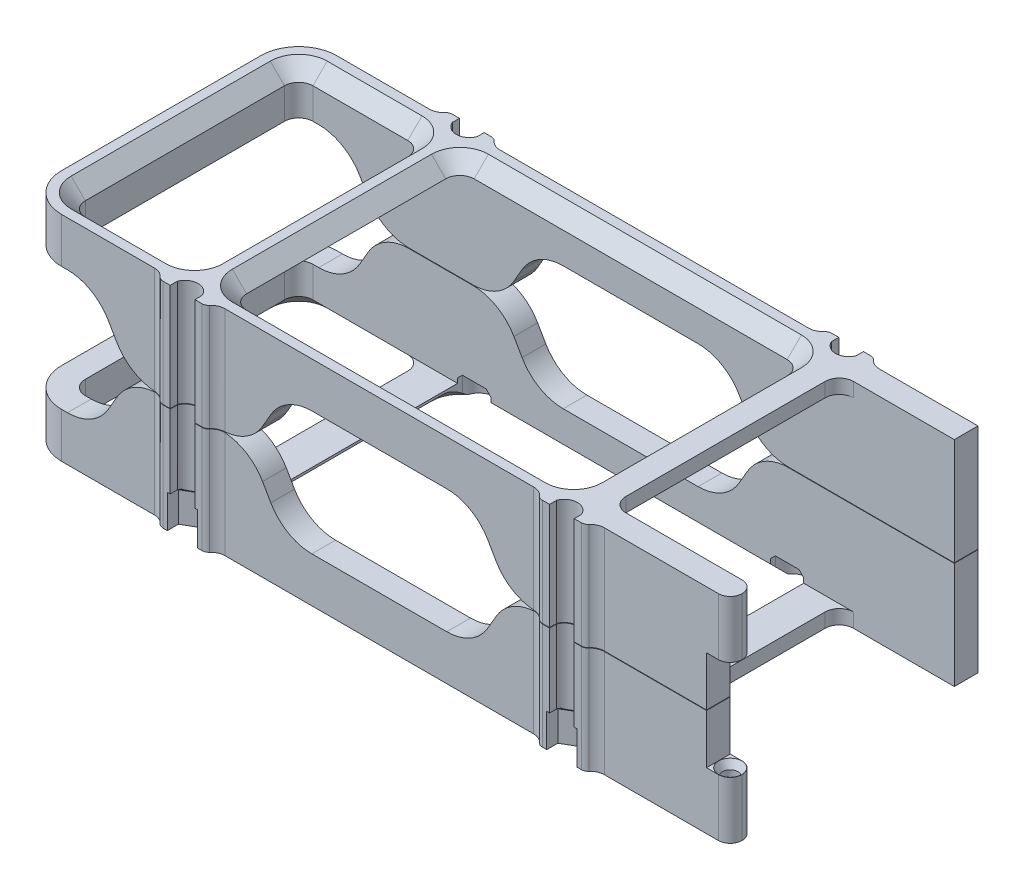
SolidWorks part; units mm, degrees
ref_plane "Płaszczyzna przednia" through (0, 0, 0) normal (0, 0, 1) x (1, 0, 0)
ref_plane "Płaszczyzna górna" through (0, 0, 0) normal (0, 1, 0) x (1, 0, 0)
ref_plane "Płaszczyzna prawa" through (0, 0, 0) normal (1, 0, 0) x (0, 0, -1)
sketch "Szkic1" plane through (0, 0, 0) normal (0, 1, 0) x (1, 0, 0)
  line L0 (-70, -24) -> (74, -24)
  line L1 (74, -24) -> (74, -29)
  line L3 (-75, -29) -> (-75, -24)
  line L4 (74, -29) -> (45.6, -29)
  line L5 (0, 29) -> (0, -29) construction
  line L6 (-34.4, -29) -> (34.4, -29)
  line L7 (-75, -29) -> (-45.6, -29)
  line L8 (-45.6, -29) -> (-40, -29) construction
  line L9 (-40, -29) -> (-34.4, -29) construction
  line L10 (34.4, -29) -> (40, -29) construction
  line L11 (45.6, -29) -> (40, -29) construction
  line L12 (-55, 0) -> (55, 0) construction
  line L13 (45.6, 29) -> (40, 29) construction
  line L14 (34.4, 29) -> (40, 29) construction
  line L15 (-40, 29) -> (-34.4, 29) construction
  line L16 (-45.6, 29) -> (-40, 29) construction
  line L17 (-75, 29) -> (-45.6, 29)
  line L18 (-34.4, 29) -> (34.4, 29)
  line L19 (68.25, 29) -> (45.6, 29)
  line L20 (-75, 29) -> (-75, 24)
  line L21 (74, 24) -> (74, 29) construction
  line L22 (-70, 24) -> (68.25, 24)
  line L23 (-75, 24) -> (-75, -24)
  line L24 (-70, 24) -> (-70, -24)
  line L25 (-75, 24) -> (-70, 24) construction
  line L26 (-75, -24) -> (-70, -24) construction
  line L27 (68.25, 29) -> (68.25, 24)
  line L28 (68.25, 24) -> (74, 24) construction
  line L29 (74, 29) -> (68.25, 29) construction
  arc A0 (-45.6, -29) -> (-34.4, -29) centre (-40, -29) ccw
  arc A1 (34.4, -29) -> (45.6, -29) centre (40, -29) ccw
  arc A2 (-34.4, -29) -> (-45.6, -29) centre (-40, -29) ccw construction
  arc A3 (45.6, -29) -> (34.4, -29) centre (40, -29) ccw construction
  arc A4 (45.6, 29) -> (34.4, 29) centre (40, 29) cw construction
  arc A5 (-34.4, 29) -> (-45.6, 29) centre (-40, 29) cw construction
  arc A6 (34.4, 29) -> (45.6, 29) centre (40, 29) cw
  arc A7 (-45.6, 29) -> (-34.4, 29) centre (-40, 29) cw
  point P4 (0, 0)
  point P12 (0, 0)
  point P16 (0, -29)
  point P31 (0, 29)
  dimension "D1" = 11.2
  dimension "D2" = 11.2
  dimension "D3" = 80
  dimension "D4" = 149
  dimension "D6" = 58
  dimension "D7" = 5
  dimension "D5" = 48
  dimension "D8" = 5.75
extrude "Dodanie-wyciągnięcie1" add sketch "Szkic1" along normal blind 22.5 separate body
sketch "Szkic2" plane through (0, 22.5, 0) normal (0, 1, 0) x (1, 0, 0)
  line L0 (-45.6, -29) -> (-42.6, -29) construction
  line L3 (-37.4, -29) -> (-34.4, -29) construction
  line L4 (-44.1, -30.5) -> (-42.6, -30.5)
  line L5 (-42.6, -29) -> (-42.6, -30.5)
  line L6 (-37.4, -29) -> (-37.4, -30.5)
  line L7 (-42.6, -30.5) -> (-42.1237, -30.5) construction
  line L8 (-42.1237, -30.5) -> (-37.8763, -30.5) construction
  line L9 (-37.8763, -30.5) -> (-37.4, -30.5) construction
  line L10 (-37.4, -30.5) -> (-35.9, -30.5)
  line L12 (-55, 0) -> (55, 0) construction
  line L13 (-37.8763, 30.5) -> (-37.4, 30.5) construction
  line L14 (-42.1237, 30.5) -> (-37.8763, 30.5) construction
  line L15 (-42.6, 30.5) -> (-42.1237, 30.5) construction
  line L16 (-37.4, 29) -> (-34.4, 29) construction
  line L22 (-45.6, 29) -> (-42.6, 29) construction
  line L23 (-37.4, 30.5) -> (-35.9, 30.5)
  line L24 (-37.4, 29) -> (-37.4, 30.5)
  line L25 (-42.6, 29) -> (-42.6, 30.5)
  line L26 (-44.1, 30.5) -> (-42.6, 30.5)
  line L27 (0, -55) -> (0, 55) construction
  line L28 (45.6, 29) -> (42.6, 29) construction
  line L29 (37.4, 29) -> (34.4, 29) construction
  line L30 (42.6, 30.5) -> (42.1237, 30.5) construction
  line L31 (42.1237, 30.5) -> (37.8763, 30.5) construction
  line L40 (37.8763, 30.5) -> (37.4, 30.5) construction
  line L41 (37.8763, -30.5) -> (37.4, -30.5) construction
  line L42 (42.1237, -30.5) -> (37.8763, -30.5) construction
  line L43 (42.6, -30.5) -> (42.1237, -30.5) construction
  line L44 (37.4, -29) -> (34.4, -29) construction
  line L45 (45.6, -29) -> (42.6, -29) construction
  line L46 (44.1, 30.5) -> (42.6, 30.5)
  line L47 (42.6, 29) -> (42.6, 30.5)
  line L48 (37.4, 29) -> (37.4, 30.5)
  line L49 (37.4, 30.5) -> (35.9, 30.5)
  line L50 (37.4, -30.5) -> (35.9, -30.5)
  line L51 (37.4, -29) -> (37.4, -30.5)
  line L52 (42.6, -29) -> (42.6, -30.5)
  line L53 (44.1, -30.5) -> (42.6, -30.5)
  arc A3 (-42.1237, -30.5) -> (-37.8763, -30.5) centre (-40, -29) ccw construction
  arc A4 (-45.6, -29) -> (-44.1, -30.5) centre (-44.1, -29) ccw
  arc A5 (-34.4, -29) -> (-35.9, -30.5) centre (-35.9, -29) cw
  arc A6 (-45.6, -29) -> (-34.4, -29) centre (-40, -29) ccw
  arc A7 (-42.6, -29) -> (-42.1237, -30.5) centre (-40, -29) ccw construction
  arc A8 (-37.8763, -30.5) -> (-37.4, -29) centre (-40, -29) ccw construction
  arc A10 (-37.8763, 30.5) -> (-37.4, 29) centre (-40, 29) cw construction
  arc A11 (-42.6, 29) -> (-42.1237, 30.5) centre (-40, 29) cw construction
  arc A12 (-42.1237, 30.5) -> (-37.8763, 30.5) centre (-40, 29) cw construction
  arc A17 (-42.6, 29) -> (-37.4, 29) centre (-40, 30) ccw
  arc A18 (-45.6, 29) -> (-34.4, 29) centre (-40, 29) cw
  arc A19 (-34.4, 29) -> (-35.9, 30.5) centre (-35.9, 29) ccw
  arc A20 (-45.6, 29) -> (-44.1, 30.5) centre (-44.1, 29) cw
  arc A21 (42.1237, 30.5) -> (37.8763, 30.5) centre (40, 29) ccw construction
  arc A22 (42.6, 29) -> (42.1237, 30.5) centre (40, 29) ccw construction
  arc A31 (-42.6, -29) -> (-37.4, -29) centre (-40, -30) cw
  arc A32 (37.8763, 30.5) -> (37.4, 29) centre (40, 29) ccw construction
  arc A33 (37.8763, -30.5) -> (37.4, -29) centre (40, -29) cw construction
  arc A34 (42.6, -29) -> (42.1237, -30.5) centre (40, -29) cw construction
  arc A35 (42.1237, -30.5) -> (37.8763, -30.5) centre (40, -29) cw construction
  arc A36 (42.6, -29) -> (37.4, -29) centre (40, -30) ccw
  arc A37 (45.6, 29) -> (44.1, 30.5) centre (44.1, 29) ccw
  arc A38 (34.4, 29) -> (35.9, 30.5) centre (35.9, 29) cw
  arc A39 (45.6, 29) -> (34.4, 29) centre (40, 29) ccw
  arc A40 (42.6, 29) -> (37.4, 29) centre (40, 30) cw
  arc A41 (45.6, -29) -> (34.4, -29) centre (40, -29) cw
  arc A42 (34.4, -29) -> (35.9, -30.5) centre (35.9, -29) ccw
  arc A43 (45.6, -29) -> (44.1, -30.5) centre (44.1, -29) cw
  dimension "D1" = 5.2
  dimension "D2" = 1
extrude "Wytnij-wyciągnięcie1" cut sketch "Szkic2" against normal through all
fillet "Zaokrąglenie1" radius 8 2 edges at (-75, 11.25, -29) (-75, 11.25, 29)
fillet "Zaokrąglenie2" radius 3 2 edges at (-70, 11.25, -24) (-70, 11.25, 24)
fillet "Zaokrąglenie3" radius 3 8 edges at (-34.4, 11.25, 29) (-45.6, 11.25, 29) (-45.6, 11.25, -29) (-34.4, 11.25, -29) (34.4, 11.25, -29) (45.6, 11.25, -29) (45.6, 11.25, 29) (34.4, 11.25, 29)
fillet "Zaokrąglenie4" radius 2.5 2 edges at (74, 11.25, 24) (74, 11.25, 29)
sketch "Szkic16" plane through (0, 0, 0) normal (0, -1, 0) x (1, 0, 0)
  line L0 (-40, 0) -> (40, 0) construction
  line L1 (40, 24) -> (40, -24) construction
  line L2 (-67, -24) -> (68.25, -24) construction
  line L4 (71.5, 24) -> (-67, 24) construction
  line L5 (44, 24) -> (44, -24)
  line L6 (44, -24) -> (40, -24)
  line L7 (36, 24) -> (44, 24)
  line L8 (36, 24) -> (36, -24)
  line L9 (36, -24) -> (40, -24)
  line L10 (0, -55) -> (0, 55) construction
  line L11 (-44, -24) -> (-40, -24)
  line L12 (-36, -24) -> (-40, -24)
  line L13 (-44, 24) -> (-44, -24)
  line L14 (-36, 24) -> (-44, 24)
  line L15 (-36, 24) -> (-36, -24)
  point P4 (0, 0)
  point P10 (40, 0)
  point P17 (40, 24)
  dimension "D1" = 80
  dimension "D2" = 8
extrude "Dodanie-wyciągnięcie6" add sketch "Szkic16" against normal blind 3
sketch "Szkic17" plane through (0, 0, 29) normal (0, 0, 1) x (1, 0, 0)
  line L0 (-75, 9.5) -> (-60, 9.5)
  line L1 (-75, 0) -> (-75, 22.5) construction
  line L2 (-60, 9.5) -> (-52.4944, 22.5)
  line L3 (-67, 22.5) -> (-47.4541, 22.5) construction
  line L4 (-52.4944, 22.5) -> (-75, 22.5)
  line L5 (-75, 22.5) -> (-75, 9.5)
  dimension "D1" = 15
  dimension "D2" = 60
  dimension "D3" = 13
extrude "Wytnij-wyciągnięcie9" cut sketch "Szkic17" against normal through all
sketch "Szkic18" plane through (0, 0, 29) normal (0, 0, 1) x (1, 0, 0)
  line L0 (-27.5056, 22.5) -> (-20, 9.5)
  line L1 (-32.5459, 22.5) -> (32.5459, 22.5) construction
  line L2 (0, 0) -> (0, 9.5) construction
  line L3 (-32.5459, 0) -> (32.5459, 0) construction
  line L4 (20, 9.5) -> (-20, 9.5)
  line L5 (20, 9.5) -> (27.5056, 22.5)
  line L6 (27.5056, 22.5) -> (-27.5056, 22.5)
  point P11 (0, 9.5)
  dimension "D1" = 60
  dimension "D2" = 60
  dimension "D3" = 40
  dimension "D4" = 13
extrude "Wytnij-wyciągnięcie10" cut sketch "Szkic18" against normal through all
fillet "Zaokrąglenie5" radius 10 12 edges at (-52.4944, 22.5, -26.5) (-52.4944, 22.5, 26.5) (-27.5056, 22.5, 26.5) (-20, 9.5, 26.5) (20, 9.5, 26.5) (27.5056, 22.5, 26.5) (-27.5056, 22.5, -26.5) (-20, 9.5, -26.5) (20, 9.5, -26.5) (27.5056, 22.5, -26.5) (-60, 9.5, -26.5) (-60, 9.5, 26.5)
fillet "Zaokrąglenie6" radius 3 8 edges at (-44, 1.5, -24) (-44, 1.5, 24) (-36, 1.5, 24) (-36, 1.5, -24) (36, 1.5, -24) (44, 1.5, -24) (36, 1.5, 24) (44, 1.5, 24)
chamfer "Sfazowanie5" distance 3 angle 45 16 edges at (-44, 0, 0) (-44.8787, 0, 23.1213) (-44.8787, 0, -23.1213) (-57, 0, 24) (-57, 0, -24) (-69.1213, 0, 23.1213) (-69.1213, 0, -23.1213) (-70, 0, 0) (36, 0, 0) (35.1213, 0, -23.1213) (35.1213, 0, 23.1213) (0, 0, -24) (0, 0, 24) (-35.1213, 0, -23.1213) (-35.1213, 0, 23.1213) (-36, 0, 0)
sketch "Szkic24" plane through (0, 22.5, 0) normal (0, 1, 0) x (1, 0, 0)
  line L4 (68.25, 29) -> (65.25, 29)
  line L5 (68.25, 29) -> (47.4541, 29) construction
  line L6 (65.25, 29) -> (65.25, 31.5)
  line L7 (65.25, 31.5) -> (68.25, 29)
  dimension "D1" = 2.5
  dimension "D2" = 3
extrude "Dodanie-wyciągnięcie7" add sketch "Szkic24" against normal blind 2.2
chamfer "Sfazowanie10" distance 3 angle 40 1 edges at (66.75, 20.3, -29) first distance on face at (66.25, 20.3, -29.8333)
fillet "Zaokrąglenie7" radius 0.2 1 edges at (65.25, 21.1902, -31.5)
ref_plane "Płaszczyzna2" through (0, 22.55, 0) normal (0, 1, 0) x (1, 0, 0)
mirror "Lustro1" about plane through (0, 22.55, 0) normal (0, 1, 0) of bodies 127 118 111
sketch "Szkic19" plane through (0, 0, 0) normal (0, -1, 0) x (1, 0, 0)
  line L1 (40, -26.305) -> (36.8, -28.1525)
  line L2 (36.8, -28.1525) -> (36.8, -31.8475)
  line L3 (36.8, -31.8475) -> (40, -33.695)
  line L4 (40, -33.695) -> (43.2, -31.8475)
  line L5 (43.2, -31.8475) -> (43.2, -28.1525)
  line L6 (43.2, -28.1525) -> (40, -26.305)
  line L7 (-40, -26.305) -> (-43.2, -28.1525)
  line L8 (-43.2, -28.1525) -> (-43.2, -31.8475)
  line L9 (-43.2, -31.8475) -> (-40, -33.695)
  line L10 (-40, -33.695) -> (-36.8, -31.8475)
  line L11 (-36.8, -31.8475) -> (-36.8, -28.1525)
  line L12 (-36.8, -28.1525) -> (-40, -26.305)
  line L13 (-40, 26.305) -> (-36.8, 28.1525)
  line L14 (-36.8, 28.1525) -> (-36.8, 31.8475)
  line L15 (-36.8, 31.8475) -> (-40, 33.695)
  line L16 (-40, 33.695) -> (-43.2, 31.8475)
  line L17 (-43.2, 31.8475) -> (-43.2, 28.1525)
  line L18 (-43.2, 28.1525) -> (-40, 26.305)
  line L19 (40, 26.305) -> (43.2, 28.1525)
  line L20 (43.2, 28.1525) -> (43.2, 31.8475)
  line L21 (43.2, 31.8475) -> (40, 33.695)
  line L22 (40, 33.695) -> (36.8, 31.8475)
  line L23 (36.8, 31.8475) -> (36.8, 28.1525)
  line L24 (36.8, 28.1525) -> (40, 26.305)
  circle A0 centre (40, -30) radius 3.2 construction
  circle A1 centre (-40, -30) radius 3.2 construction
  circle A2 centre (-40, 30) radius 3.2 construction
  circle A3 centre (40, 30) radius 3.2 construction
  dimension "D1" = 6.4
  dimension "D2" = 6.4
  dimension "D3" = 6.4
  dimension "D4" = 6.4
extrude "Wytnij-wyciągnięcie11" cut sketch "Szkic19" against normal blind 7
chamfer "Sfazowanie6" distance 0.7 angle 45 8 edges at (-38.4, 7, 27.2287) (-41.6, 7, 27.2287) (-41.6, 7, -27.2287) (-38.4, 7, -27.2287) (38.4, 7, -27.2287) (41.6, 7, -27.2287) (41.6, 7, 27.2287) (38.4, 7, 27.2287)
sketch "Szkic20" plane through (0, 0, 0) normal (0, -1, 0) x (1, 0, 0)
  line L0 (0, 0) -> (33, 0) construction
  line L1 (33, 25) -> (33, -25) construction
  line L2 (36.5, 25) -> (36.5, -25)
  line L3 (29.5, 25) -> (29.5, -25)
  line L5 (0, -12.375) -> (0, 12.375) construction
  line L6 (-33, 25) -> (-33, -25) construction
  line L7 (-36.5, 25) -> (-36.5, -25)
  line L8 (-29.5, 25) -> (-29.5, -25)
  arc A0 (36.5, 25) -> (29.5, 25) centre (33, 25) ccw
  arc A1 (29.5, -25) -> (36.5, -25) centre (33, -25) ccw
  arc A2 (-36.5, 25) -> (-29.5, 25) centre (-33, 25) cw
  arc A3 (-29.5, -25) -> (-36.5, -25) centre (-33, -25) cw
  point P5 (33, 0)
  point P16 (-33, 0)
  dimension "D1" = 7
  dimension "D2" = 33
  dimension "D3" = 50
extrude "Wytnij-wyciągnięcie12" cut sketch "Szkic20" against normal blind 5
chamfer "Sfazowanie7" distance 1 angle 45 12 edges at (36.5, 5, 24.5) (29.5, 5, 24.5) (33, 5, 28.5) (29.5, 5, -24.5) (36.5, 5, -24.5) (33, 5, -28.5) (-29.5, 5, 24.5) (-36.5, 5, 24.5) (-33, 5, 28.5) (-36.5, 5, -24.5) (-29.5, 5, -24.5) (-33, 5, -28.5)
sketch "Szkic21" plane through (0, 22.55, 0) normal (0, 1, 0) x (1, 0, 0)
  circle A0 centre (71.5, -26.5) radius 1.6
  arc A1 (71.5, -29) -> (74, -26.5) centre (71.5, -26.5) ccw construction
  dimension "D1" = 0.9
  dimension "D2" = 3.2
extrude "Wytnij-wyciągnięcie13" cut sketch "Szkic21" against normal blind 20.5 and the other way blind 20.5
sketch "Szkic22" plane through (0, 22.55, 0) normal (0, 1, 0) x (1, 0, 0)
  line L0 (69, -29) -> (69, -24)
  line L1 (69, -29) -> (74, -29)
  line L2 (69, -24) -> (74, -24)
  line L3 (74, -29) -> (74, -24)
  line L4 (69, -29) -> (74, -24) construction
  line L5 (69, -24) -> (74, -29) construction
  point P1 (71.5, -26.5)
  dimension "D1" = 5
  dimension "D2" = 5
extrude "Wytnij-wyciągnięcie14" cut sketch "Szkic22" against normal blind 10.5 and the other way blind 10.5
chamfer "Sfazowanie8" distance 1.5 angle 30 1 edges at (71.5, 12.05, 28.1) first distance on face at (71.5, 2.05, 28.1)
chamfer "Sfazowanie9" distance 1.5 angle 30 1 edges at (71.5, 33.05, 28.1) first distance on face at (71.5, 33.05, 28.1)
equation "\"Rod_diameter\"= 5.2"
equation "\"D2@Szkic1\"=\"Rod_diameter\"+6"
equation "\"D1@Szkic2\"=\"Rod_diameter\""
equation "\"height\"=22.5"
equation "\"D1@Dodanie-wyciągnięcie1\"=\"height\""
